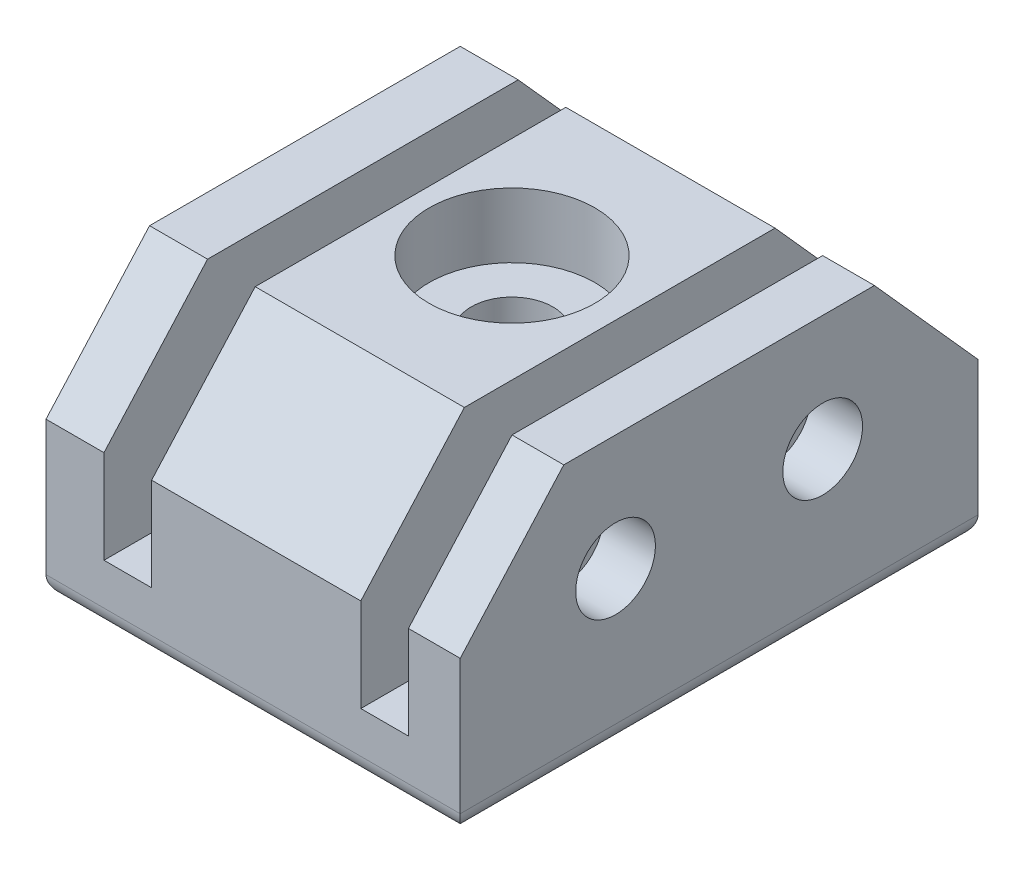
SolidWorks part; units mm, degrees
ref_plane "Front Plane" through (0, 0, 0) normal (0, 0, 1) x (1, 0, 0)
ref_plane "Top Plane" through (0, 0, 0) normal (0, 1, 0) x (1, 0, 0)
ref_plane "Right Plane" through (0, 0, 0) normal (1, 0, 0) x (0, 0, -1)
sketch "Sketch1" plane through (0, 0, 0) normal (1, 0, 0) x (0, 0, -1)
  line L1 (0, 0) -> (63.5, 0)
  line L2 (0, 0) -> (0, 6.35)
  line L3 (0, 6.35) -> (63.5, 6.35)
  line L4 (63.5, 0) -> (63.5, 6.35)
  dimension "D1" = 6.35
  dimension "D2" = 63.5
extrude "Boss-Extrude1" add sketch "Sketch1" against normal blind 50.8
sketch "Sketch2" plane through (0, 0, 0) normal (1, 0, 0) x (0, 0, -1)
  line L0 (0, 6.35) -> (0, 19.05)
  line L1 (0, 19.05) -> (12.7, 33.249)
  line L2 (12.7, 33.249) -> (50.8, 33.249)
  line L3 (50.8, 33.249) -> (63.5, 19.05)
  line L4 (63.5, 19.05) -> (63.5, 6.35)
  line L5 (63.5, 6.35) -> (0, 6.35)
  point P7 (31.75, 33.249)
  point P10 (31.75, 6.35)
  dimension "D1" = 38.1
  dimension "D2" = 12.7
  dimension "D3" = 12.7
  dimension "D4" = 19.05
  dimension "D5" = 19.05
extrude "Boss-Extrude2" add sketch "Sketch2" against normal blind 50.8
sketch "Sketch10" plane through (0, 0, -63.5) normal (0, 0, -1) x (-1, 0, 0)
  line L1 (50.8, 33.249) -> (0, 33.249) construction
  line L3 (6.35, 7.62) -> (6.35, 33.249)
  line L4 (6.35, 33.249) -> (12.192, 33.249)
  line L5 (12.192, 7.62) -> (12.192, 33.249)
  line L6 (6.35, 7.62) -> (12.192, 7.62)
  line L8 (50.8, 0) -> (0, 0) construction
  point P11 (12.192, 7.62)
  dimension "D1" = 7.62
  dimension "D2" = 5.842
  dimension "D3" = 6.35
extrude "Cut-Extrude1" cut sketch "Sketch10" against normal through all
pattern_linear "LPattern3" count 2 spacing 31.496 along (-1, 0, 0) of "Cut-Extrude1"
sketch "Sketch11" plane through (0, 0, 0) normal (1, 0, 0) x (0, 0, -1)
  circle A0 centre (19.05, 19.05) radius 4.8895
  circle A1 centre (19.05, 19.05) radius 7.9375 construction
  circle A2 centre (44.45, 19.05) radius 4.8895
  circle A3 centre (44.45, 19.05) radius 7.9375 construction
  dimension "D1" = 9.779
  dimension "D3" = 15.875
  dimension "D4" = 9.779
  dimension "D6" = 15.875
  dimension "D2" = 6.35
  dimension "D5" = 6.35
extrude "Cut-Extrude2" cut sketch "Sketch11" against normal through all
sketch "Sketch14" plane through (0, 33.249, 0) normal (0, 1, 0) x (1, 0, 0)
  line L3 (-37.846, 12.7) -> (-37.846, 50.8) construction
  point P0 (-25.4, 31.75)
  point P4 (-37.846, 31.75)
  dimension "D1" = 12.446
sketch "Sketch17" plane through (0, 40.0201, -44.7438) normal (0, 0.6667, -0.7454) x (-1, 0, 0)
  line L0 (12.192, -28.1343) -> (12.192, -9.0843) construction
  line L1 (37.846, -9.0843) -> (12.192, -9.0843) construction
  point P0 (25.019, -18.6093)
  point P4 (12.192, -18.6093)
  point P7 (25.019, -9.0843)
sketch "Sketch18" plane through (0, 8.4667, 9.466) normal (0, 0.6667, 0.7454) x (1, 0, 0)
  line L0 (-12.192, 33.249) -> (-12.192, 14.199) construction
  line L1 (-37.846, 33.249) -> (-12.192, 33.249) construction
  point P0 (-25.019, 23.724)
  point P1 (-25.019, 23.724)
  point P4 (-12.192, 23.724)
  point P7 (-25.019, 33.249)
ref_plane "Plane2" through (0, 33.02, 0) normal (0, -1, 0) x (-1, 0, 0)
fillet "Fillet1" radius 2.54 4 edges at (0, 0, -31.75) (-50.8, 0, -31.75) (-25.4, 0, 0) (-25.4, 0, -63.5)
sketch "Sketch22" plane through (0, 33.249, 0) normal (0, -1, 0) x (1, 0, 0)
  line L1 (-25.4, -63.5) -> (-25.4, 0) construction
  line L2 (-50.8, -63.5) -> (0, -63.5) construction
  line L3 (-50.8, 0) -> (0, 0) construction
  line L4 (0, -31.75) -> (-50.8, -31.75) construction
  line L6 (0, 0) -> (0, -63.5) construction
  line L7 (-50.8, 0) -> (-50.8, -63.5) construction
  circle A1 centre (-25.4, -31.75) radius 10.16
  dimension "D1" = 20.32
extrude "Cut-Extrude8" cut sketch "Sketch22" along normal blind 7.9375
sketch "Sketch24" plane through (0, 0, 0) normal (0, -1, 0) x (1, 0, 0)
  line L0 (-25.4, -63.5) -> (-25.4, 0) construction
  line L1 (-50.8, -63.5) -> (0, -63.5) construction
  line L2 (-50.8, 0) -> (0, 0) construction
  line L3 (0, -31.75) -> (-50.8, -31.75) construction
  line L4 (0, 0) -> (0, -63.5) construction
  line L5 (-50.8, 0) -> (-50.8, -63.5) construction
  circle A0 centre (-25.4, -31.75) radius 5
  dimension "D1" = 10
extrude "Cut-Extrude10" cut sketch "Sketch24" against normal through all
sketch "Sketch25" plane through (0, 0, 0) normal (0, -1, 0) x (1, 0, 0)
  circle A0 centre (-25.4, -31.75) radius 10.16
  dimension "D1" = 20.32
extrude "Cut-Extrude11" cut sketch "Sketch25" against normal blind 2.54
